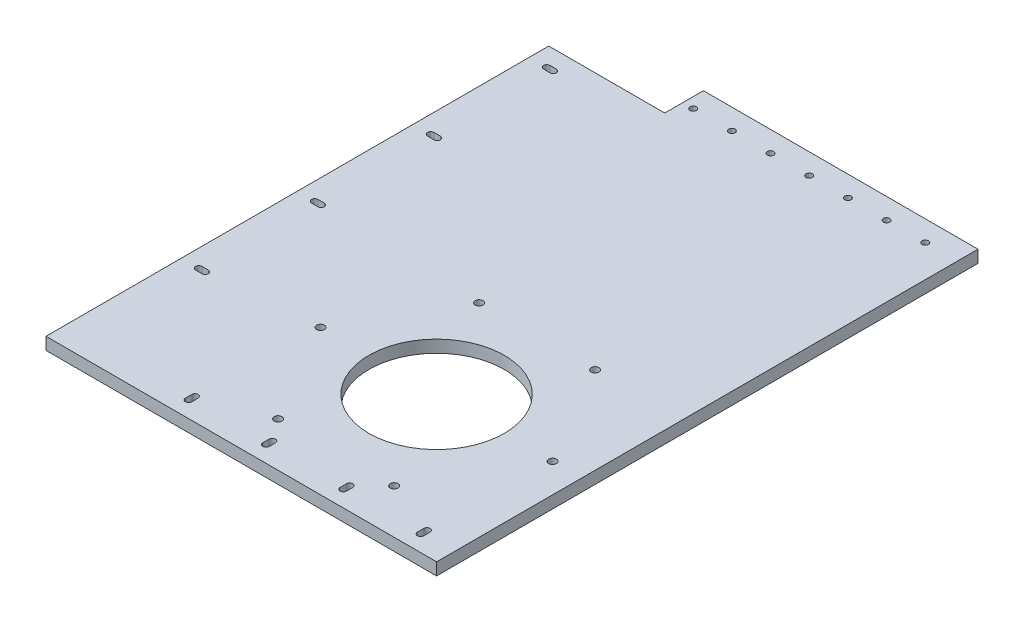
SolidWorks part; units mm, degrees
ref_plane "Front Plane" through (0, 0, 0) normal (0, 0, 1) x (1, 0, 0)
ref_plane "Top Plane" through (0, 0, 0) normal (0, 1, 0) x (1, 0, 0)
ref_plane "Right Plane" through (0, 0, 0) normal (1, 0, 0) x (0, 0, -1)
sketch "Sketch1" plane through (0, 0, 0) normal (0, 1, 0) x (1, 0, 0)
  line L3 (-71, 140) -> (71, 140)
  line L4 (71, -140) -> (71, 140)
  line L5 (0, 140) -> (0, -135) construction
  line L6 (0, 0) -> (71, 0) construction
  line L10 (-71, 140) -> (-71, 120)
  line L11 (-71, 120) -> (-131, 120)
  line L12 (-131, 120) -> (-131, -140)
  line L13 (-131, -140) -> (71, -140)
  point P0 (0, 0)
  dimension "D1" = 280
  dimension "D2" = 20
  dimension "D3" = 202
  dimension "D4" = 60
extrude "Boss-Extrude1" add sketch "Sketch1" along normal blind 6.35
sketch "Sketch2" plane through (0, 6.35, 0) normal (0, 1, 0) x (1, 0, 0)
  line L1 (0, 140) -> (0, -140) construction
  line L2 (71, 140) -> (-71, 140) construction
  line L3 (-131, -140) -> (71, -140) construction
  circle A0 centre (0, -65) radius 41.5 construction
  circle A1 centre (0, -23.5) radius 2.25
  circle A2 centre (29.3449, -35.6551) radius 2.25
  circle A3 centre (41.5, -65) radius 2.25
  circle A4 centre (29.3449, -94.3449) radius 2.25
  circle A5 centre (0, -106.5) radius 2.25
  circle A6 centre (-29.3449, -94.3449) radius 2.25
  circle A7 centre (-41.5, -65) radius 2.25
  circle A8 centre (-29.3449, -35.6551) radius 2.25
  circle A9 centre (0, -65) radius 80 construction
  circle A10 centre (0, -65) radius 30
  point P22 (0, -65)
  dimension "D1" = 83
  dimension "D2" = 4.5
  dimension "D4" = 160
  dimension "D6" = 60
  dimension "D5" = 75
  dimension "D3" = 8
extrude "Cut-Extrude1" [suppressed] cut sketch "Sketch2" against normal through all
sketch "Sketch6" [suppressed] plane through (0, 6.35, 0) normal (0, 1, 0) x (1, 0, 0)
  line L0 (0, -65) -> (-38.9712, -46.8274) construction
  line L1 (0, -65) -> (0, -23.5) construction
  line L2 (-40.9787, -51.1324) -> (-36.9638, -42.5225) construction
  line L3 (-36.9638, -42.5225) -> (-27.9007, -46.7486) construction
  circle A0 centre (0, -65) radius 30 construction
  circle A1 centre (-36.9638, -42.5225) radius 0.85
  circle A2 centre (-40.9787, -51.1324) radius 0.85
  circle A5 centre (-29.9082, -51.0536) radius 0.85
  point P7 (-38.9712, -46.8274)
  dimension "D4" = 1.7
  dimension "D5" = 10
  dimension "D7" = 10
  dimension "D6" = 1.7
  dimension "D1" = 43
  dimension "D2" = 9.5
  dimension "D3" = 65
extrude "Cut-Extrude5" [suppressed] cut sketch "Sketch6" against normal through all
sketch "Sketch8" [suppressed] plane through (0, 6.35, 0) normal (0, 1, 0) x (1, 0, 0)
  line L1 (71, 140) -> (-71, 140) construction
  line L2 (65, -20.6305) -> (65, 140) construction
  line L3 (71, -140) -> (71, 140) construction
  line L5 (45, 41.8036) -> (45, 140) construction
  circle A0 centre (0, 65) radius 25
  circle A1 centre (0, -65) radius 30 construction
  dimension "D1" = 130
  dimension "D2" = 50
  dimension "D3" = 6
  dimension "D4" = 20
extrude "Cut-Extrude9" [suppressed] cut sketch "Sketch8" against normal through all
sketch "Sketch9" plane through (0, 0, 0) normal (0, -1, 0) x (-1, 0, 0)
  circle A1 centre (45.6, 129.325) radius 1.65
  circle A2 centre (5.6, 129.325) radius 1.65
  circle A3 centre (-34.4, 129.325) radius 1.65
  circle A4 centre (65.6, 129.325) radius 1.65
  circle A5 centre (25.6, 129.325) radius 1.65
  circle A6 centre (-14.4, 129.325) radius 1.65
  circle A7 centre (-54.4, 129.325) radius 1.65
extrude "Cut-Extrude10" cut sketch "Sketch9" against normal blind 30
sketch "Sketch10" plane through (0, 0, 0) normal (0, -1, 0) x (1, 0, 0)
  line L0 (-121.975, 10) -> (-118.675, 10) construction
  line L3 (-121.975, 11.65) -> (-118.675, 11.65)
  line L4 (-121.975, 8.35) -> (-118.675, 8.35)
  line L5 (-121.975, 70) -> (-118.675, 70) construction
  line L6 (-121.975, 71.65) -> (-118.675, 71.65)
  line L7 (-121.975, 68.35) -> (-118.675, 68.35)
  line L8 (-121.975, -50) -> (-118.675, -50) construction
  line L9 (-121.975, -48.35) -> (-118.675, -48.35)
  line L10 (-121.975, -51.65) -> (-118.675, -51.65)
  line L11 (-121.975, -110) -> (-118.675, -110) construction
  line L12 (-121.975, -108.35) -> (-118.675, -108.35)
  line L13 (-121.975, -111.65) -> (-118.675, -111.65)
  circle A0 centre (-120.325, -110) radius 1.65
  circle A1 centre (-120.325, -50) radius 1.65
  circle A2 centre (-120.325, 10) radius 1.65
  circle A3 centre (-120.325, 70) radius 1.65
  arc A6 (-121.975, 11.65) -> (-121.975, 8.35) centre (-121.975, 10) ccw
  arc A7 (-118.675, 8.35) -> (-118.675, 11.65) centre (-118.675, 10) ccw
  arc A8 (-121.975, 71.65) -> (-121.975, 68.35) centre (-121.975, 70) ccw
  arc A9 (-118.675, 68.35) -> (-118.675, 71.65) centre (-118.675, 70) ccw
  arc A10 (-121.975, -48.35) -> (-121.975, -51.65) centre (-121.975, -50) ccw
  arc A11 (-118.675, -51.65) -> (-118.675, -48.35) centre (-118.675, -50) ccw
  arc A12 (-121.975, -108.35) -> (-121.975, -111.65) centre (-121.975, -110) ccw
  arc A13 (-118.675, -111.65) -> (-118.675, -108.35) centre (-118.675, -110) ccw
  point P14 (-120.325, 10)
  point P21 (-120.325, 70)
  point P28 (-120.325, -50)
  point P35 (-120.325, -110)
  dimension "D1" = 3.3
  dimension "D2" = 3.3
  dimension "D3" = 3.3
  dimension "D4" = 3.3
  dimension "D5" = 1.65
  dimension "D6" = 1.65
  dimension "D7" = 1.65
  dimension "D8" = 1.65
sketch "Sketch11" plane through (0, 6.35, 0) normal (0, 1, 0) x (1, 0, 0)
  line L0 (71, -127.15) -> (-131, -127.15) construction
  line L1 (71, -140) -> (71, 140) construction
  line L2 (456.625, -127.15) -> (-127.825, -127.15) construction
  line L3 (-131, 120) -> (-131, -140) construction
  line L4 (71, -132.85) -> (-131, -132.85) construction
  line L5 (456.625, -132.85) -> (-127.825, -132.85) construction
  line L6 (-65.6, 129.325) -> (-65.6, -130.005) construction
  line L7 (-65.6, -130.005) -> (71, -130) construction
  line L8 (456.625, -130) -> (-127.825, -130) construction
  line L9 (-25.6, 129.325) -> (-25.6, -130.0035) construction
  line L10 (14.4, 129.325) -> (14.4, -130.0021) construction
  line L11 (54.4, 129.325) -> (54.4, -130.0006) construction
  line L12 (-65.6, -128.355) -> (-65.6, -131.655) construction
  line L13 (-63.95, -128.355) -> (-63.95, -131.655)
  line L14 (-67.25, -128.355) -> (-67.25, -131.655)
  line L15 (-25.6, -128.3535) -> (-25.6, -131.6535) construction
  line L16 (-23.95, -128.3535) -> (-23.95, -131.6535)
  line L17 (-27.25, -128.3535) -> (-27.25, -131.6535)
  line L18 (14.4, -128.3521) -> (14.4, -131.6521) construction
  line L19 (16.05, -128.3521) -> (16.05, -131.6521)
  line L20 (12.75, -128.3521) -> (12.75, -131.6521)
  line L21 (54.4, -128.3506) -> (54.4, -131.6506) construction
  line L22 (56.05, -128.3506) -> (56.05, -131.6506)
  line L23 (52.75, -128.3506) -> (52.75, -131.6506)
  circle A0 centre (-65.6, -130.005) radius 1.65 construction
  circle A1 centre (-25.6, -130.0035) radius 1.65 construction
  circle A2 centre (14.4, -130.0021) radius 1.65 construction
  circle A3 centre (54.4, -130.0006) radius 1.65 construction
  arc A4 (-63.95, -128.355) -> (-67.25, -128.355) centre (-65.6, -128.355) ccw
  arc A5 (-67.25, -131.655) -> (-63.95, -131.655) centre (-65.6, -131.655) ccw
  arc A6 (-23.95, -128.3535) -> (-27.25, -128.3535) centre (-25.6, -128.3535) ccw
  arc A7 (-27.25, -131.6535) -> (-23.95, -131.6535) centre (-25.6, -131.6535) ccw
  arc A8 (16.05, -128.3521) -> (12.75, -128.3521) centre (14.4, -128.3521) ccw
  arc A9 (12.75, -131.6521) -> (16.05, -131.6521) centre (14.4, -131.6521) ccw
  arc A10 (56.05, -128.3506) -> (52.75, -128.3506) centre (54.4, -128.3506) ccw
  arc A11 (52.75, -131.6506) -> (56.05, -131.6506) centre (54.4, -131.6506) ccw
  point P33 (-65.6, -130.005)
  point P39 (-25.6, -130.0035)
  point P46 (14.4, -130.0021)
  point P53 (54.4, -130.0006)
  dimension "D2" = 3.3
  dimension "D1" = 259.33
extrude "Cut-Extrude12" cut sketch "Sketch11" against normal blind 30
extrude "Cut-Extrude13" cut sketch "Sketch10" against normal blind 10 contours A0 | L13 A13 L12 A0 | L12 A12 L13 A0 | L9 A10 L10 A1 | A1 | L10 A11 L9 A1 | L3 A6 L4 A2 | A2 | L4 A7 L3 A2 | L6 A8 L7 A3 | A3 | L7 A9 L6 A3 region at (-122.4459, 0, 10) region at (-118.2041, 0, 10) region at (-120.325, 0, 10) region at (-122.4459, 0, 70) region at (-118.2041, 0, 70) region at (-120.325, 0, 70) region at (-122.4459, 0, -50) region at (-118.2041, 0, -50) region at (-120.325, 0, -50) region at (-122.4459, 0, -110) region at (-118.2041, 0, -110) region at (-120.325, 0, -110)
sketch "Sketch12" plane through (0, 6.35, 0) normal (0, 1, 0) x (1, 0, 0)
  line L0 (-131, -140) -> (71, -140) construction
  line L1 (71, -140) -> (71, 140) construction
  circle A0 centre (-4, -65) radius 35
  point P2 (0, 0)
  point P3 (0, -72.5072)
  point P8 (26.7369, -68.8818)
  dimension "D1" = 70
  dimension "D2" = 75
  dimension "D3" = 75
extrude "Cut-Extrude14" cut sketch "Sketch12" against normal through all
sketch "Sketch13" plane through (0, 6.35, 0) normal (0, 1, 0) x (1, 0, 0)
  line L0 (-69, -65) -> (-59, -65) construction
  circle A2 centre (-4, -65) radius 65 construction
  circle A3 centre (-64, -65) radius 2
  circle A4 centre (-34, -13.0385) radius 2
  circle A5 centre (-4, -65) radius 65 construction
  circle A6 centre (26, -13.0385) radius 2
  circle A7 centre (-4, -65) radius 65 construction
  circle A8 centre (56, -65) radius 2
  circle A9 centre (-4, -65) radius 65 construction
  circle A10 centre (26, -116.9615) radius 2
  circle A11 centre (-4, -65) radius 65 construction
  circle A12 centre (-34, -116.9615) radius 2
  circle A13 centre (-4, -65) radius 65 construction
  circle A14 centre (-4, -65) radius 55 construction
  circle A15 centre (-4, -65) radius 35 construction
  point P2 (0, 0)
  point P8 (-71.3174, -68.4861)
  point P9 (0, 0)
  point P25 (-4, -65)
  dimension "D1" = 130
  dimension "D2" = 4
  dimension "D3" = 6
  dimension "D4" = 110
extrude "Cut-Extrude15" cut sketch "Sketch13" against normal through all
